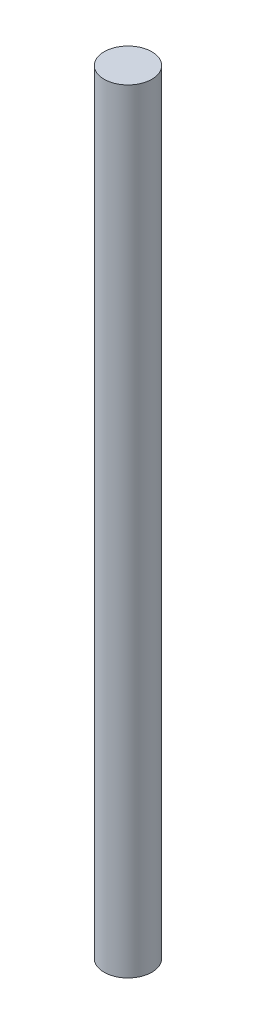
SolidWorks part; units mm, degrees
ref_plane "Front Plane" through (0, 0, 0) normal (0, 0, 1) x (1, 0, 0)
ref_plane "Top Plane" through (0, 0, 0) normal (0, 1, 0) x (1, 0, 0)
ref_plane "Right Plane" through (0, 0, 0) normal (1, 0, 0) x (0, 0, -1)
sketch "Sketch1" plane through (0, 0, 0) normal (0, 1, 0) x (1, 0, 0)
  circle A0 centre (0, 0) radius 1.45
  dimension "D1" = 2.9
extrude "Boss-Extrude1" add sketch "Sketch1" along normal blind 47
